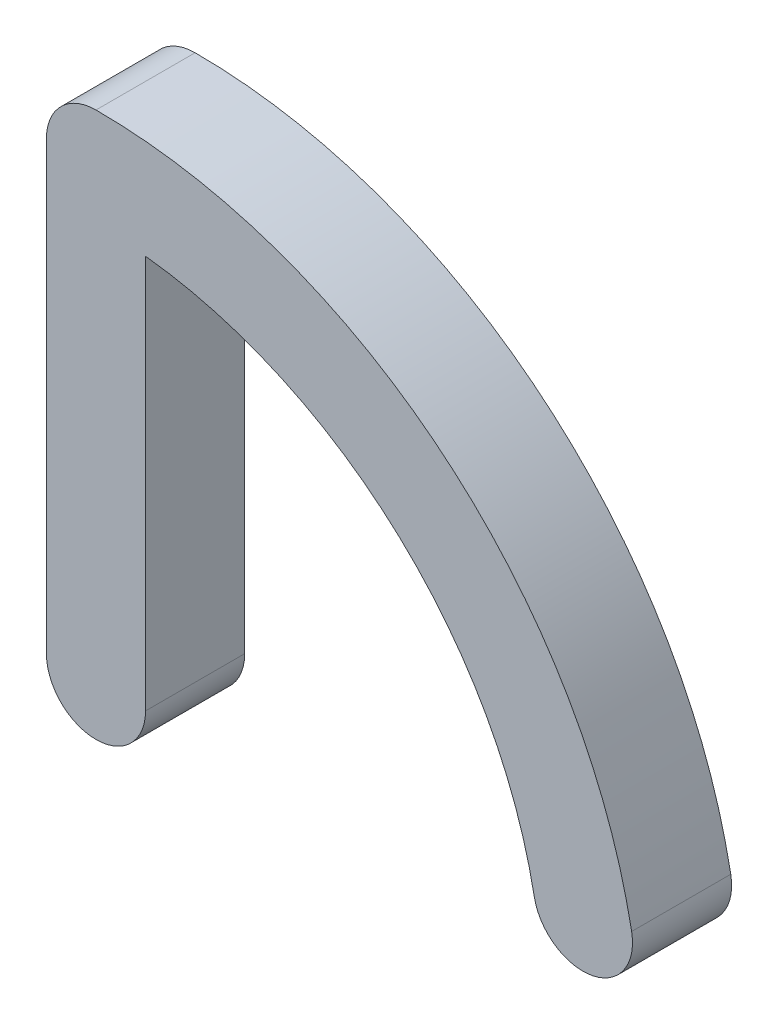
SolidWorks part; units mm, degrees
ref_plane "Front Plane" through (0, 0, 0) normal (0, 0, 1) x (1, 0, 0)
ref_plane "Top Plane" through (0, 0, 0) normal (0, 1, 0) x (1, 0, 0)
ref_plane "Right Plane" through (0, 0, 0) normal (1, 0, 0) x (0, 0, -1)
sketch "Sketch1" plane through (0, 0, 0) normal (0, 0, 1) x (1, 0, 0)
  line L0 (0, 0) -> (0, 50)
  line L1 (0, 0) -> (49.8097, 4.3578) construction
  arc A0 (0, 50) -> (49.8097, 4.3578) centre (0, 0) cw
  dimension "D1" = 50
  dimension "D2" = 85
extrude "Extrude-Thin1" add sketch "Sketch1" along normal blind 10 thin
fillet "Fillet1" radius 5 1 edges at (-5, 54.7723, 5)
fillet "Fillet2" radius 5 1 edges at (54.7907, 4.7936, 5)
fillet "Fillet3" radius 5 1 edges at (44.8288, 3.922, 5)
fillet "Fillet4" radius 5 1 edges at (5, 0, 5)
fillet "Fillet5" radius 5 1 edges at (-5, 0, 5)
sketch "Sketch2" plane through (0, 0, 0) normal (0, 0, -1) x (-1, 0, 0)
  line L0 (1.924, 19.3472) -> (2.921, 7.1374) construction
  line L1 (-2.921, 7.1374) -> (-1.924, 19.3472) construction
  line L2 (1.924, 19.3472) -> (2.921, 7.1374)
  line L3 (-2.921, 7.1374) -> (-1.924, 19.3472)
  arc A0 (1.924, 19.3472) -> (-1.924, 19.3472) centre (0, 19.1901) ccw construction
  circle A1 centre (0, 5) radius 3.6195 construction
  arc A2 (1.924, 19.3472) -> (-1.924, 19.3472) centre (0, 19.1901) ccw
  arc A3 (-2.921, 7.1374) -> (2.921, 7.1374) centre (0, 5) ccw
extrude "Cut-Extrude1" cut sketch "Sketch2" against normal blind 4.5
